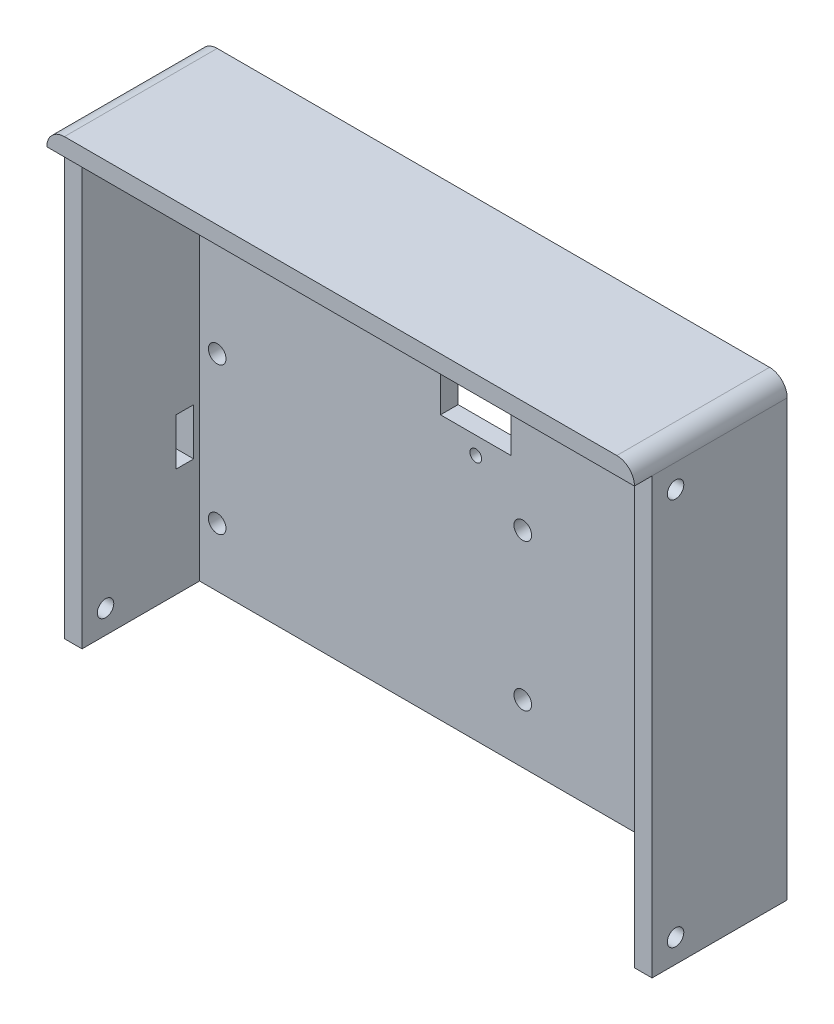
SolidWorks part; units mm, degrees
ref_plane "正面" through (0, 0, 0) normal (0, 0, 1) x (1, 0, 0)
ref_plane "平面" through (0, 0, 0) normal (0, 1, 0) x (1, 0, 0)
ref_plane "右側面" through (0, 0, 0) normal (1, 0, 0) x (0, 0, -1)
sketch "Sketch1" plane through (0, 0, 0) normal (0, 0, 1) x (1, 0, 0)
  line L1 (0, 0) -> (-100, 0)
  line L2 (0, 0) -> (0, 77)
  line L3 (0, 77) -> (-100, 77)
  line L4 (-100, 0) -> (-100, 77)
  dimension "D1" = 100
  dimension "D2" = 77
extrude "Boss-Extrude1" add sketch "Sketch1" along normal blind 3
sketch "Sketch2" plane through (0, 0, 3) normal (0, 0, 1) x (1, 0, 0)
  line L0 (-100, 0) -> (0, 0) construction
  line L1 (-100, 77) -> (-97, 77)
  line L2 (-100, 77) -> (-100, 0)
  line L3 (-100, 0) -> (-97, 0)
  line L4 (-97, 74) -> (-97, 0)
  line L6 (0, 77) -> (-3, 77)
  line L7 (0, 77) -> (0, 0)
  line L8 (0, 0) -> (-3, 0)
  line L9 (-3, 74) -> (-3, 0)
  line L10 (-3, 77) -> (-97, 77)
  line L12 (-3, 74) -> (-97, 74)
  dimension "D1" = 3
  dimension "D2" = 3
  dimension "D3" = 3
extrude "Boss-Extrude2" add sketch "Sketch2" along normal blind 20
sketch "Sketch3" plane through (0, 0, 23) normal (0, 0, 1) x (1, 0, 0)
  line L0 (-100, 77) -> (-100, 0) construction
  line L1 (0, 77) -> (-100, 77)
  line L2 (0, 77) -> (0, 74)
  line L3 (0, 74) -> (-100, 74)
  line L4 (-100, 77) -> (-100, 74)
  line L5 (-97, 74) -> (-3, 74) construction
extrude "Boss-Extrude3" add sketch "Sketch3" along normal blind 3
sketch "Sketch4" plane through (0, 0, 0) normal (0, 0, -1) x (-1, 0, 0)
  line L0 (0, 77) -> (100, 77) construction
  line L1 (44, 68) -> (56, 68)
  line L2 (44, 68) -> (44, 45)
  line L3 (44, 45) -> (56, 45)
  line L4 (56, 68) -> (56, 45)
  line L5 (0, 0) -> (0, 77) construction
  line L6 (100, 77) -> (100, 0) construction
  dimension "D1" = 9
  dimension "D2" = 44
  dimension "D3" = 44
  dimension "D4" = 23
extrude "Cut-Extrude1" cut sketch "Sketch4" against normal blind 3
sketch "Sketch5" plane through (0, 0, 0) normal (0, 0, -1) x (-1, 0, 0)
  line L0 (100, 77) -> (100, 0) construction
  line L1 (100, 0) -> (0, 0) construction
  circle A0 centre (94, 10) radius 1.5
  dimension "D2" = 3
  dimension "D1" = 6
  dimension "D3" = 10
extrude "Cut-Extrude2" cut sketch "Sketch5" against normal through all contours A0
pattern_linear "LPattern1" count 2 spacing 25 along (0, 1, 0) count 2 spacing 52 along (1, 0, 0) of "Cut-Extrude2"
sketch "Sketch6" plane through (0, 0, 0) normal (1, 0, 0) x (0, 0, -1)
  line L0 (-23, 0) -> (0, 0) construction
  line L1 (-23, 0) -> (-23, 74) construction
  circle A0 centre (-19, 4) radius 1.4
  dimension "D3" = 2.8
  dimension "D1" = 4
  dimension "D2" = 4
extrude "Cut-Extrude3" cut sketch "Sketch6" against normal through all
sketch "Sketch7" plane through (-100, 0, 0) normal (-1, 0, 0) x (0, 0, 1)
  line L0 (23, 0) -> (0, 0) construction
  line L1 (4, 26.5) -> (7, 26.5)
  line L2 (4, 26.5) -> (4, 18.5)
  line L3 (4, 18.5) -> (7, 18.5)
  line L4 (7, 26.5) -> (7, 18.5)
  line L5 (0, 77) -> (0, 0) construction
  dimension "D1" = 3
  dimension "D2" = 8
  dimension "D3" = 18.5
  dimension "D4" = 7
extrude "Cut-Extrude4" cut sketch "Sketch7" against normal up to next contours L1 L4 L3 L2
sketch "Sketch9" plane through (0, 0, 0) normal (0, 0, -1) x (-1, 0, 0)
  line L2 (56, 68) -> (44, 68) construction
  line L3 (44, 68) -> (44, 45) construction
  circle A0 centre (50, 71) radius 1
  dimension "D1" = 2
  dimension "D2" = 3
  dimension "D3" = 6
ref_plane "Plane2" through (0, 56.5, 0) normal (0, -1, 0) x (-1, 0, 0)
extrude "Cut-Extrude5" cut sketch "Sketch9" against normal up to next contours A0
mirror "Mirror1" about plane through (0, 56.5, 0) normal (0, -1, 0) of "Cut-Extrude5"
ref_plane "Plane3" through (0, 37, 0) normal (0, -1, 0) x (-1, 0, 0)
mirror "Mirror2" about plane through (0, 37, 0) normal (0, -1, 0) of "Cut-Extrude3"
fillet "Fillet1" radius 3 2 edges at (0, 77, 13) (-100, 77, 13)
